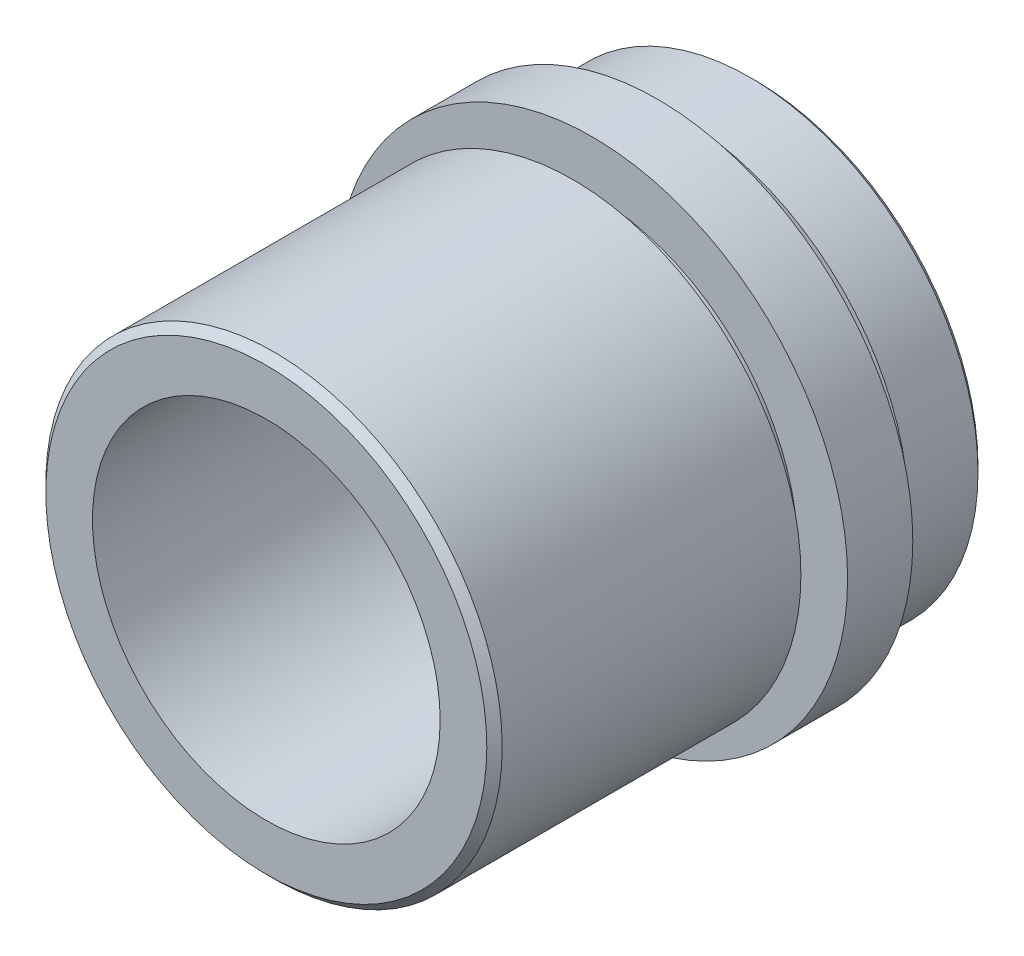
SolidWorks part; units mm, degrees
ref_plane "Płaszczyzna przednia" through (0, 0, 0) normal (0, 0, 1) x (1, 0, 0)
ref_plane "Płaszczyzna górna" through (0, 0, 0) normal (0, 1, 0) x (1, 0, 0)
ref_plane "Płaszczyzna prawa" through (0, 0, 0) normal (1, 0, 0) x (0, 0, -1)
sketch "Szkic1" plane through (0, 0, 0) normal (1, 0, 0) x (0, 0, -1)
  line L0 (-15, 0) -> (-15, 23.5)
  line L1 (-15, 23.5) -> (-9, 23.5)
  line L2 (-9, 23.5) -> (-9, 0)
  line L3 (-9, 0) -> (-15, 0)
  line L4 (-9, 0) -> (-15, 0) construction
sketch "Szkic2" plane through (0, 0, 0) normal (1, 0, 0) x (0, 0, -1)
  line L0 (-45, 0) -> (-45, 21)
  line L1 (-45, 21) -> (-15, 21)
  line L2 (-15, 21) -> (-15, 0)
  line L3 (-15, 0) -> (-45, 0)
  line L4 (-15, 0) -> (-45, 0) construction
sketch "Szkic3" plane through (0, 0, 0) normal (1, 0, 0) x (0, 0, -1)
  line L0 (-45, 20.2929) -> (-44.2929, 21)
  line L1 (-44.2929, 21) -> (-45, 21)
  line L2 (-45, 21) -> (-45, 20.2929)
  line L3 (-15, 0) -> (-45, 0) construction
sketch "Szkic4" plane through (0, 0, 0) normal (1, 0, 0) x (0, 0, -1)
  line L0 (-16.8, 21) -> (-16.8, 18.9)
  line L1 (-16.8, 18.9) -> (-15, 18.9)
  line L2 (-15, 18.9) -> (-15, 21)
  line L3 (-15, 21) -> (-16.8, 21)
  line L4 (-15, 0) -> (-45, 0) construction
ref_plane "Płaszczyzna1" through (0, 0, 9) normal (0, 0, 1) x (1, 0, 0)
ref_plane "Płaszczyzna2" through (0, 0, 45) normal (0, 0, 1) x (1, 0, 0)
sketch "Szkic5" plane through (0, 0, 0) normal (1, 0, 0) x (0, 0, -1)
  line L0 (-9, 0) -> (-9, 21)
  line L1 (-9, 21) -> (0, 21)
  line L2 (0, 21) -> (0, 0)
  line L3 (0, 0) -> (-9, 0)
  line L4 (0, 0) -> (-9, 0) construction
sketch "Szkic6" plane through (0, 0, 0) normal (1, 0, 0) x (0, 0, -1)
  line L0 (-45, 0) -> (-45, 16)
  line L1 (-45, 16) -> (-1, 16)
  line L2 (-1, 16) -> (0, 17)
  line L3 (0, 17) -> (0, 0)
  line L4 (0, 0) -> (-45, 0)
  line L5 (0, 0) -> (-45, 0) construction
sketch "Szkic7" plane through (0, 0, 0) normal (1, 0, 0) x (0, 0, -1)
  line L0 (-0.5, 21) -> (0, 20.5)
  line L1 (0, 20.5) -> (0, 21)
  line L2 (0, 21) -> (-0.5, 21)
  line L3 (0, 0) -> (-9, 0) construction
sketch "Szkic8" plane through (0, 0, 0) normal (1, 0, 0) x (0, 0, -1)
  line L0 (-9, 18.9) -> (-6.9, 18.9)
  line L1 (-6.9, 18.9) -> (-6.9, 21)
  line L2 (-6.9, 21) -> (-9, 21)
  line L3 (-9, 21) -> (-9, 18.9)
  line L4 (0, 0) -> (-9, 0) construction
revolve "Obrót1" add sketch "Szkic1" angle 360 about L4 reverse direction yes
revolve "Obrót2" add sketch "Szkic2" angle 360 about L4 reverse direction yes
revolve "Wycięcie-obrót1" cut sketch "Szkic3" angle 360 about L3 reverse direction yes
revolve "Wycięcie-obrót2" cut sketch "Szkic4" angle 360 about L4 reverse direction yes
revolve "Obrót3" add sketch "Szkic5" angle 360 about L4 reverse direction yes
revolve "Wycięcie-obrót3" cut sketch "Szkic6" angle 360 about L5 reverse direction yes
revolve "Wycięcie-obrót4" cut sketch "Szkic7" angle 360 about L3 reverse direction yes
revolve "Wycięcie-obrót5" cut sketch "Szkic8" angle 360 about L4 reverse direction yes
ref_plane "IP1 XY" through (0, 0, 9) normal (0, 0, 1) x (1, 0, 0)
ref_plane "IP1 XZ" through (0, 0, 0) normal (0, -1, 0) x (-1, 0, 0)
ref_plane "IP1 YZ" through (0, 0, 0) normal (1, 0, 0) x (0, 0, -1)
ref_axis "IP1 X" through (-80.9, 0, 9) along (1, 0, 0)
ref_axis "IP1 Y" through (0, -50, 9) along (0, 1, 0)
ref_axis "IP1 Z" through (0, 0, 80.9) along (0, 0, -1)
sketch3d "IP1"
  point P0 (0, 0, 9)
ref_plane "IP2 XY" through (0, 0, 45) normal (0, 0, 1) x (1, 0, 0)
ref_plane "IP2 XZ" through (0, 0, 0) normal (0, -1, 0) x (-1, 0, 0)
ref_plane "IP2 YZ" through (0, 0, 0) normal (1, 0, 0) x (0, 0, -1)
ref_axis "IP2 X" through (-80.9, 0, 45) along (1, 0, 0)
ref_axis "IP2 Y" through (0, -50, 45) along (0, 1, 0)
ref_axis "IP2 Z" through (0, 0, 80.9) along (0, 0, -1)
sketch3d "IP2"
  point P0 (0, 0, 45)
ref_plane "IP3 XY" through (0, 0, 0) normal (0, 0, 1) x (1, 0, 0)
ref_plane "IP3 XZ" through (0, 0, 0) normal (0, -1, 0) x (-1, 0, 0)
ref_plane "IP3 YZ" through (0, 0, 0) normal (1, 0, 0) x (0, 0, -1)
ref_axis "IP3 X" through (-80.9, 0, 0) along (1, 0, 0)
ref_axis "IP3 Y" through (0, -50, 0) along (0, 1, 0)
ref_axis "IP3 Z" through (0, 0, 80.9) along (0, 0, -1)
sketch3d "IP3"
  point P0 (0, 0, 0)
